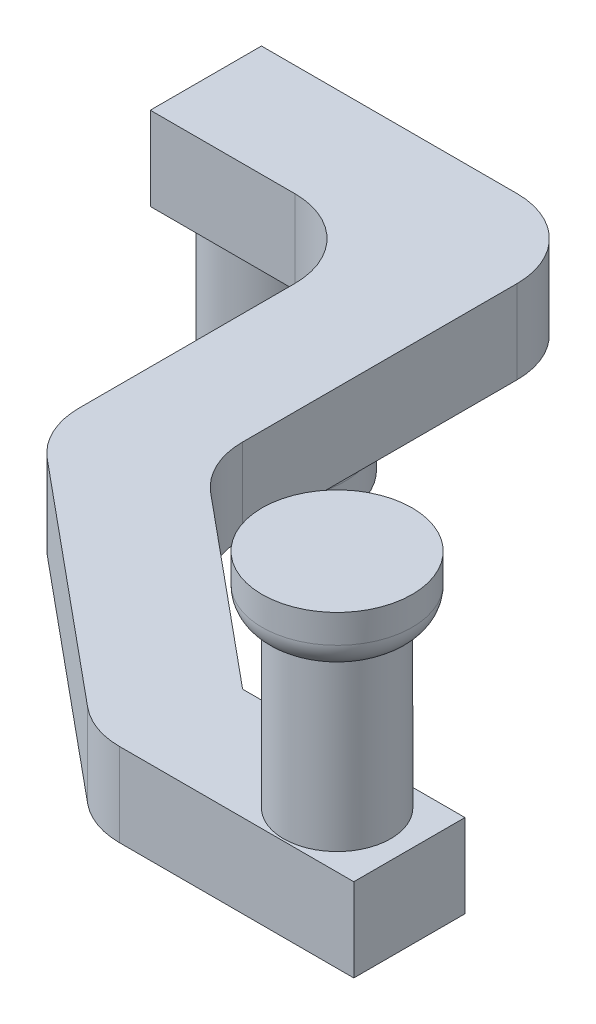
SolidWorks part; units mm, degrees
ref_plane "Front Plane" through (0, 0, 0) normal (0, 0, 1) x (1, 0, 0)
ref_plane "Top Plane" through (0, 0, 0) normal (0, 1, 0) x (1, 0, 0)
ref_plane "Right Plane" through (0, 0, 0) normal (1, 0, 0) x (0, 0, -1)
sketch "Sketch1" plane through (0, 0, 0) normal (0, 1, 0) x (1, 0, 0)
  line L0 (0, 0) -> (6, 0)
  line L1 (6, 0) -> (6, -7)
  line L2 (6, -7) -> (9.8505, -10.1896)
  line L3 (9.8505, -10.1896) -> (13.8505, -10.1896)
  line L4 (0, -2) -> (4, -2)
  line L5 (4, -2) -> (4, -7.9403)
  line L6 (4, -7.9403) -> (9.1297, -12.1896)
  line L7 (9.1297, -12.1896) -> (13.8505, -12.1896)
  line L8 (13.8505, -10.1896) -> (13.8505, -12.1896)
  line L9 (0, 0) -> (0, -2)
  point P11 (13.76, -11.974)
  point P12 (17.9539, -12.5652)
  point P13 (7, -9.161)
  point P14 (9, -6.8477)
  point P15 (13.0207, -12.8207)
  dimension "D1" = 6
  dimension "D2" = 7
  dimension "D3" = 5
  dimension "D4" = 4
  dimension "D5" = 2
extrude "Boss-Extrude1" add sketch "Sketch1" along normal blind 1.5
fillet "Fillet1" radius 1.4 5 edges at (6, 0.75, 7) (4, 0.75, 7.9403) (4, 0.75, 2) (6, 0.75, 0) (9.1297, 0.75, 12.1896)
sketch "Sketch2" plane through (0, 1.5, 0) normal (0, 1, 0) x (1, 0, 0)
  line L0 (13.8505, -10.1896) -> (9.8505, -10.1896) construction
  line L1 (13.8505, -12.1896) -> (13.8505, -10.1896) construction
  circle A0 centre (12.5505, -11.1896) radius 0.9631
  point P4 (16.3416, -11.8207)
  dimension "D1" = 1
  dimension "D2" = 1.3
extrude "Boss-Extrude2" add sketch "Sketch2" along normal blind 3
sketch "Sketch3" plane through (0, 4.5, 0) normal (0, 1, 0) x (1, 0, 0)
  circle A0 centre (12.5505, -11.1896) radius 1.35
extrude "Boss-Extrude3" add sketch "Sketch3" along normal blind 1
fillet "Fillet2" radius 0.5 1 edges at (12.5505, 4.5, 12.5396)
sketch "Sketch4" plane through (0, 0, 0) normal (0, -1, 0) x (-1, 0, 0)
  circle A0 centre (-1.1759, -0.9924) radius 0.9631
extrude "Boss-Extrude4" add sketch "Sketch4" along normal blind 3
sketch "Sketch5" plane through (0, -3, 0) normal (0, -1, 0) x (1, 0, 0)
  circle A0 centre (1.1927, 1.0322) radius 1.35
extrude "Boss-Extrude5" add sketch "Sketch5" along normal blind 1
fillet "Fillet3" radius 0.5 1 edges at (1.1927, -3, -0.3178)
